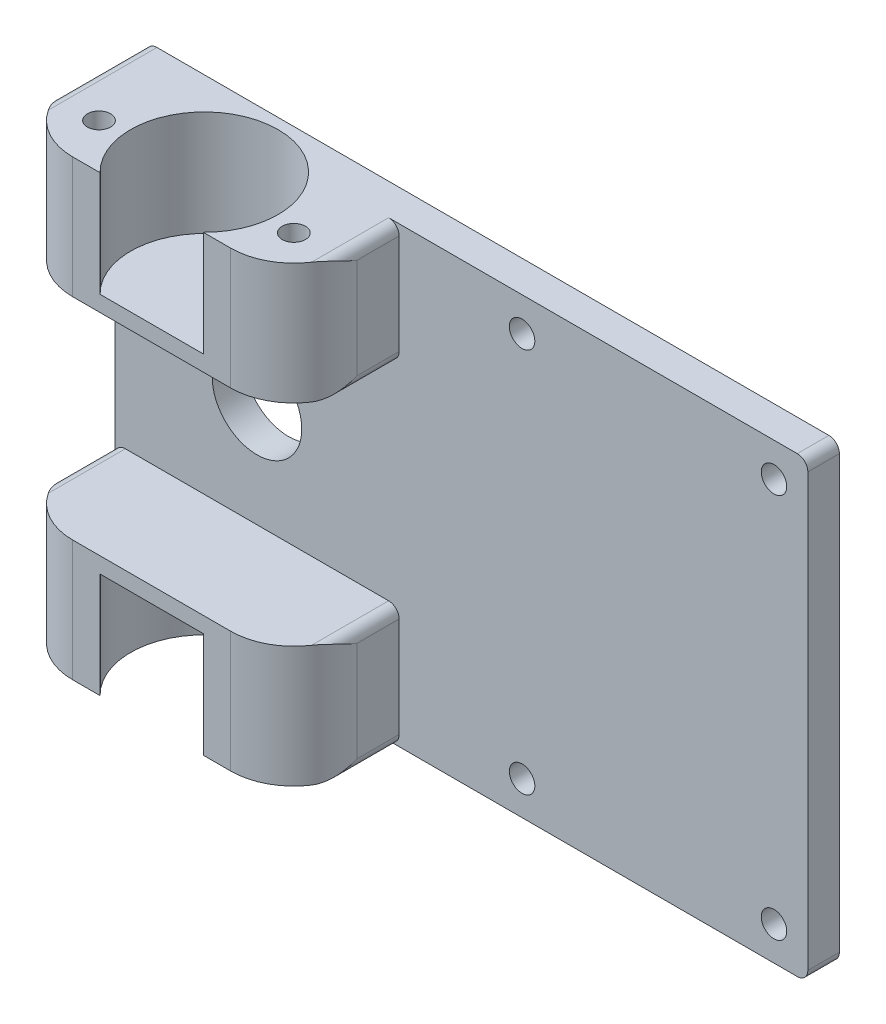
SolidWorks part; units mm, degrees
ref_plane "Přední rovina" through (0, 0, 0) normal (0, 0, 1) x (1, 0, 0)
ref_plane "Horní rovina" through (0, 0, 0) normal (0, 1, 0) x (1, 0, 0)
ref_plane "Pravá rovina" through (0, 0, 0) normal (1, 0, 0) x (0, 0, -1)
sketch "Skica2" plane through (0, 0, 0) normal (0, 0, 1) x (1, 0, 0)
  line L1 (2, 0) -> (129.6, 0)
  line L2 (0, 2) -> (0, 84)
  line L3 (2, 86) -> (129.6, 86)
  line L4 (131.6, 2) -> (131.6, 84)
  arc A0 (129.6, 86) -> (131.6, 84) centre (129.6, 84) cw
  arc A1 (129.6, 0) -> (131.6, 2) centre (129.6, 2) ccw
  arc A2 (2, 0) -> (0, 2) centre (2, 2) cw
  arc A3 (0, 84) -> (2, 86) centre (2, 84) cw
  point P7 (131.6, 86)
  point P12 (0, 0)
  point P15 (0, 86)
  dimension "D3" = 2
  dimension "D1" = 86
  dimension "D2" = 131.6
extrude "Přidat vysunutím1" add sketch "Skica2" along normal blind 6
sketch "Skica3" plane through (0, 0, 6) normal (0, 0, 1) x (1, 0, 0)
  line L0 (0, 84) -> (0, 2) construction
  line L1 (0, 43) -> (131.6, 43) construction
  line L2 (131.6, 2) -> (131.6, 84) construction
  line L3 (129.6, 86) -> (2, 86) construction
  line L4 (2, 0) -> (129.6, 0) construction
  line L5 (54, 86) -> (54, 0) construction
  circle A0 centre (27, 43) radius 8.5
  circle A1 centre (125.18, 79.58) radius 2.42
  circle A3 centre (77.34, 6.42) radius 2.42
  circle A4 centre (125.18, 6.42) radius 2.42
  circle A6 centre (77.34, 79.58) radius 2.42
  point P2 (0, 43)
  point P23 (54, 43)
  point P24 (54, 86)
  dimension "D1" = 17
  dimension "D3" = 4.84
  dimension "D4" = 6.42
  dimension "D2" = 27
  dimension "D5" = 6.42
  dimension "D6" = 6.42
  dimension "D7" = 54
  dimension "D8" = 47.84
extrude "Odebrat vysunutím1" cut sketch "Skica3" against normal blind 6
sketch "Skica4" plane through (0, 0, 6) normal (0, 0, 1) x (1, 0, 0)
  line L1 (2, 86) -> (54, 86)
  line L2 (0, 84) -> (0, 63)
  line L3 (0, 63) -> (52, 63)
  line L4 (54, 86) -> (54, 65)
  line L5 (2, 0) -> (54, 0)
  line L6 (0, 2) -> (0, 23)
  line L7 (0, 23) -> (52, 23)
  line L8 (54, 0) -> (54, 21)
  line L9 (0, 84) -> (0, 2) construction
  line L10 (129.6, 86) -> (2, 86) construction
  line L11 (2, 0) -> (129.6, 0) construction
  arc A0 (2, 86) -> (0, 84) centre (2, 84) ccw
  arc A1 (2, 0) -> (0, 2) centre (2, 2) cw
  arc A2 (52, 63) -> (54, 65) centre (52, 65) ccw
  arc A3 (52, 23) -> (54, 21) centre (52, 21) cw
  point P18 (0, 86)
  point P21 (0, 0)
  point P24 (54, 63)
  dimension "D3" = 2
  dimension "D4" = 2
  dimension "D1" = 54
  dimension "D2" = 23
extrude "Přidat vysunutím3" add sketch "Skica4" along normal blind 20
sketch "Skica6" plane through (0, 0, 0) normal (0, -1, 0) x (1, 0, 0)
  line L0 (2, 0) -> (129.6, 0) construction
  line L1 (0, 26) -> (0, 0) construction
  line L3 (2, 26) -> (54, 26) construction
  circle A0 centre (27, 16) radius 14
  point P5 (27, 16)
  point P7 (27, 26)
  dimension "D1" = 28
  dimension "D2" = 16
  dimension "D3" = 27
extrude "Odebrat vysunutím2" cut sketch "Skica6" against normal blind 20
sketch "Skica10" plane through (0, 86, 0) normal (0, 1, 0) x (1, 0, 0)
  line L1 (129.6, 0) -> (2, 0) construction
  line L2 (0, -26) -> (0, 0) construction
  line L3 (54, -26) -> (2, -26) construction
  circle A0 centre (27, -16) radius 14
  point P0 (27, -26)
  dimension "D1" = 28
  dimension "D2" = 16
  dimension "D3" = 27
extrude "Odebrat vysunutím3" cut sketch "Skica10" against normal blind 20
fillet "Zaoblit20" radius 2 4 edges at (0, 63, 16) (0, 23, 16) (54, 86, 16) (54, 0, 16)
sketch "Skica11" plane through (0, 0, 0) normal (0, 0, -1) x (-1, 0, 0)
  line L0 (-125.18, 6.42) -> (-77.34, 79.58) construction
  line L1 (-125.18, 79.58) -> (-77.34, 6.42) construction
  line L3 (-120.26, 60.5) -> (-82.26, 60.5)
  line L4 (-120.26, 60.5) -> (-120.26, 25.5)
  line L5 (-120.26, 25.5) -> (-82.26, 25.5)
  line L6 (-82.26, 60.5) -> (-82.26, 25.5)
  point P12 (-101.26, 43)
  point P13 (-101.26, 60.5)
  point P14 (-82.26, 43)
  dimension "D1" = 35
  dimension "D2" = 38
extrude "Odebrat vysunutím5" cut sketch "Skica11" against normal blind 1.2
sketch "Skica12" plane through (0, 0, 1.2) normal (0, 0, -1) x (-1, 0, 0)
  line L0 (-120.26, 60.5) -> (-120.26, 25.5) construction
  line L1 (-82.26, 60.5) -> (-120.26, 60.5) construction
  line L2 (-120.26, 25.5) -> (-82.26, 25.5) construction
  line L3 (-82.26, 25.5) -> (-82.26, 60.5) construction
  circle A0 centre (-116.76, 57) radius 2.2
  circle A1 centre (-85.76, 57) radius 2.2
  circle A2 centre (-116.76, 29) radius 2.2
  circle A3 centre (-85.76, 29) radius 2.2
  dimension "D1" = 4.4
  dimension "D2" = 3.5
  dimension "D3" = 3.5
  dimension "D4" = 3.5
  dimension "D5" = 3.5
extrude "Odebrat vysunutím6" cut sketch "Skica12" against normal blind 3
sketch "Skica14" plane through (0, 0, 0) normal (0, -1, 0) x (1, 0, 0)
  line L0 (2, 0) -> (129.6, 0) construction
  circle A0 centre (8.5, 17.5) radius 2.2
  circle A1 centre (45.5, 17.5) radius 2.2
  arc A2 (17.202, 26) -> (36.798, 26) centre (27, 16) ccw construction
  arc A3 (17.202, 26) -> (36.798, 26) centre (27, 16) ccw construction
  dimension "D1" = 4.4
  dimension "D2" = 17.5
  dimension "D3" = 18.5
  dimension "D4" = 18.5
extrude "Odebrat vysunutím7" cut sketch "Skica14" against normal blind 5
fillet "Zaoblit22" radius 12 4 edges at (54, 74.5, 26) (54, 11.5, 26) (0, 74.5, 26) (0, 11.5, 26) tangent propagation no
sketch "Skica15" plane through (0, 86, 0) normal (0, 1, 0) x (1, 0, 0)
  line L0 (129.6, 0) -> (2, 0) construction
  circle A0 centre (8.5, -17.5) radius 2.2
  circle A1 centre (45.5, -17.5) radius 2.2
  arc A2 (36.798, -26) -> (17.202, -26) centre (27, -16) ccw construction
  arc A3 (36.798, -26) -> (17.202, -26) centre (27, -16) ccw construction
  dimension "D1" = 4.4
  dimension "D2" = 17.5
  dimension "D3" = 18.5
  dimension "D4" = 18.5
extrude "Odebrat vysunutím8" cut sketch "Skica15" against normal blind 5
